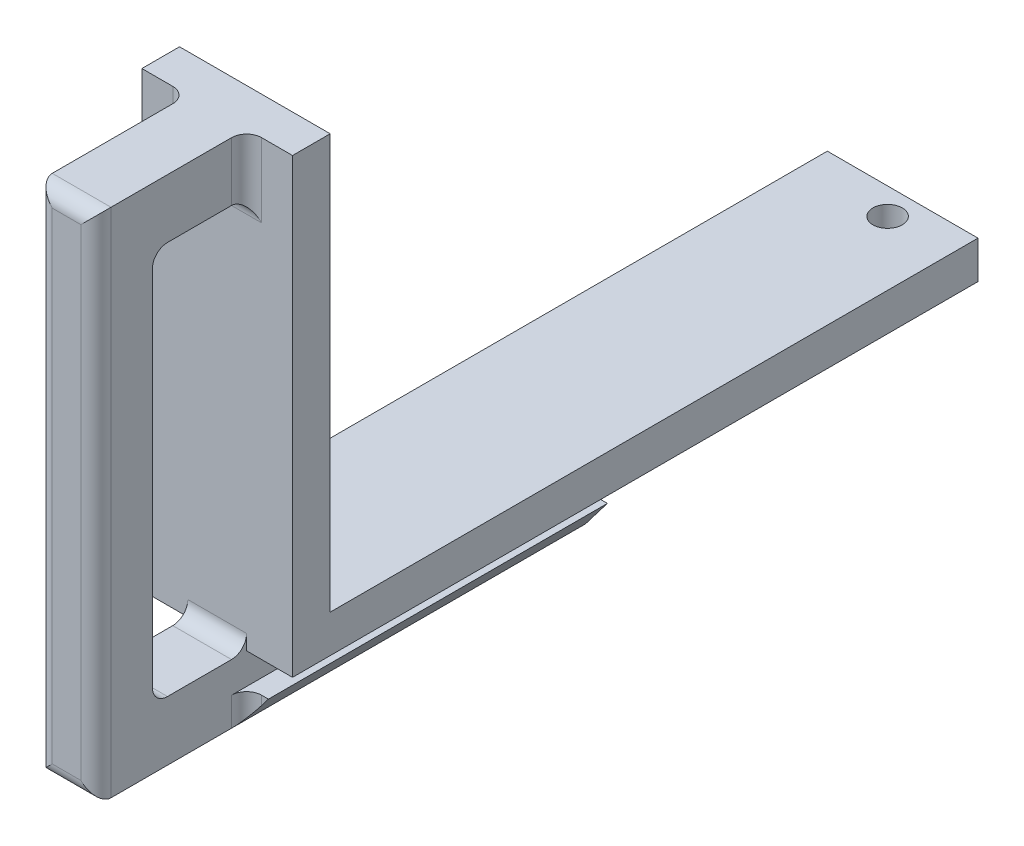
SolidWorks part; units mm, degrees
note: The reader was unsure of these and kept them because the rebuilt part matched: shared geometry of "Sketch4<2>".
ref_plane "Front Plane" through (0, 0, 0) normal (0, 0, 1) x (1, 0, 0)
ref_plane "Top Plane" through (0, 0, 0) normal (0, 1, 0) x (1, 0, 0)
ref_plane "Right Plane" through (0, 0, 0) normal (1, 0, 0) x (0, 0, -1)
sketch "Sketch1" plane through (0, 0, 0) normal (0, 1, 0) x (1, 0, 0)
  line L1 (-10, -43) -> (10, -43)
  line L2 (-10, -43) -> (-10, 43)
  line L3 (-10, 43) -> (10, 43)
  line L4 (10, -43) -> (10, 43)
  line L5 (-10, -43) -> (10, 43) construction
  line L6 (-10, 43) -> (10, -43) construction
  point P0 (0, 0)
  dimension "D1" = 20
  dimension "D2" = 86
extrude "Boss-Extrude1" add sketch "Sketch1" along normal blind 5
sketch "Sketch2" plane through (0, 5, 0) normal (0, 1, 0) x (1, 0, 0)
  line L0 (10, 0) -> (-10, 0) construction
  line L1 (10, -43) -> (10, 43) construction
  line L2 (-10, 43) -> (-10, -43) construction
  circle A0 centre (1.5, -39.5) radius 1.95
  circle A1 centre (1.5, 39.5) radius 1.95
  dimension "D1" = 3.9
  dimension "D2" = 11.5
  dimension "D3" = 79
sketch "Sketch4" plane through (0, 0, 43) normal (0, 0, 1) x (1, 0, 0)
  line L0 (0, 0) -> (0, -2.9) construction
  line L1 (-3.9, 0) -> (-3.9, -4.1)
  line L2 (-10, 0) -> (10, 0) construction
  line L3 (-3.9, -4.1) -> (-6.8, -4.1)
  line L4 (-6.8, -4.1) -> (-3.9, -7.9)
  line L5 (-3.9, -7.9) -> (3.9, -7.9)
  line L6 (3.9, -7.9) -> (6.8, -4.1)
  line L7 (6.8, -4.1) -> (3.9, -4.1)
  line L8 (3.9, -4.1) -> (3.9, 0)
  line L9 (-3.9, 0) -> (3.9, 0)
  line L10 (0, 5) -> (0, -7.9) construction
  line L11 (-10, 5) -> (10, 5) construction
  dimension "D1" = 7.8
  dimension "D2" = 2.9
  dimension "D3" = 4.1
  dimension "D4" = 3.8
extrude "Boss-Extrude4" add sketch "Sketch4" against normal blind 40
extrude "Cut-Extrude1" cut sketch "Sketch2" against normal blind 6
extrude "Boss-Extrude5" add sketch "Sketch4<2>" along normal blind 5
sketch "Sketch4<2>" plane through (0, 0, 43) normal (0, 0, 1) x (1, 0, 0) same geometry as "Sketch4"
sketch "Sketch5" plane through (0, 0, 0) normal (0, 1, 0) x (1, 0, 0)
  line L0 (10, -43) -> (10, 43) construction
  line L1 (-10, -43) -> (10, -43)
  line L2 (-10, -43) -> (-10, -48)
  line L3 (-10, -48) -> (10, -48)
  line L4 (10, -43) -> (10, -48)
  line L5 (3.9, -48) -> (-3.9, -48) construction
extrude "Boss-Extrude7" add sketch "Sketch5" along normal blind 60
sketch "Sketch6" plane through (0, 0, 48) normal (0, 0, 1) x (1, 0, 0)
  line L0 (0, 60) -> (0, -7.9) construction
  line L1 (-10, 60) -> (10, 60) construction
  line L2 (-3.9, -7.9) -> (3.9, -7.9) construction
  line L4 (-3.9, -7.9) -> (3.9, -7.9)
  line L5 (-3.9, -7.9) -> (-3.9, 0)
  line L6 (-3.9, 0) -> (3.9, 0)
  line L7 (3.9, -7.9) -> (3.9, 0)
  line L8 (-3.9, -7.9) -> (3.9, 0) construction
  line L9 (-3.9, 0) -> (3.9, -7.9) construction
  line L10 (-3.9, 52.2) -> (3.9, 52.2)
  line L11 (-3.9, 52.2) -> (-3.9, 60)
  line L12 (-3.9, 60) -> (3.9, 60)
  line L13 (3.9, 52.2) -> (3.9, 60)
  line L14 (-3.9, 52.2) -> (3.9, 60) construction
  line L15 (-3.9, 60) -> (3.9, 52.2) construction
  point P6 (0, -3.95)
  point P12 (0, 56.1)
extrude "Boss-Extrude8" add sketch "Sketch6" along normal blind 12.5
sketch "Sketch7" plane through (0, 0, 60.5) normal (0, 0, 1) x (1, 0, 0)
  line L1 (-3.9, 60) -> (3.9, 60)
  line L2 (-3.9, 60) -> (-3.9, -7.9)
  line L3 (-3.9, -7.9) -> (3.9, -7.9)
  line L4 (3.9, 60) -> (3.9, -7.9)
extrude "Boss-Extrude9" add sketch "Sketch7" along normal blind 7.5
fillet "Fillet2" radius 2 11 edges at (0, 60, 68) (3.9, 26.05, 68) (0, -7.9, 68) (-3.9, 26.05, 68) (0, 0, 60.5) (0, 52.2, 48) (-3.9, 56.1, 48) (3.9, -6, 48) (0, 0, 48) (3.9, 56.1, 48) (0, 52.2, 60.5)
